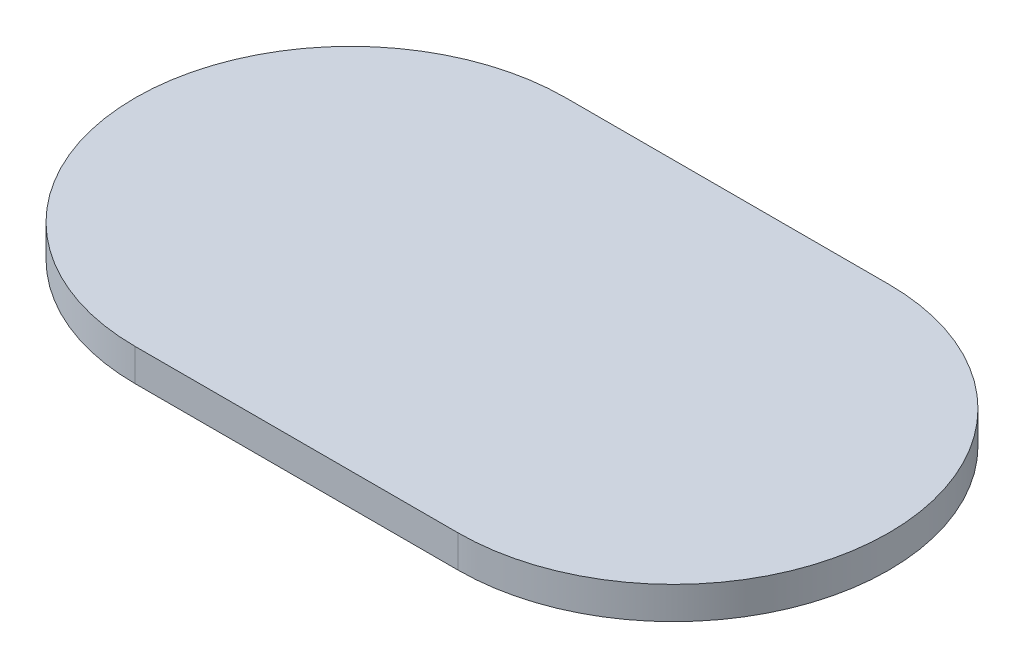
SolidWorks part; units mm, degrees
ref_plane "Front Plane" through (0, 0, 0) normal (0, 0, 1) x (1, 0, 0)
ref_plane "Top Plane" through (0, 0, 0) normal (0, 1, 0) x (1, 0, 0)
ref_plane "Right Plane" through (0, 0, 0) normal (1, 0, 0) x (0, 0, -1)
sketch "Sketch2" plane through (0, 0, 0) normal (0, 1, 0) x (1, 0, 0)
  line L0 (15, 0) -> (-15, 0) construction
  line L1 (15, 20) -> (-15, 20)
  line L2 (15, -20) -> (-15, -20)
  arc A0 (15, 20) -> (15, -20) centre (15, 0) cw
  arc A1 (-15, 20) -> (-15, -20) centre (-15, 0) ccw
  point P4 (0, 0)
  dimension "D1" = 30
  dimension "D2" = 20
  dimension "D3" = 20
extrude "Boss-Extrude1" add sketch "Sketch2" along normal blind 3
